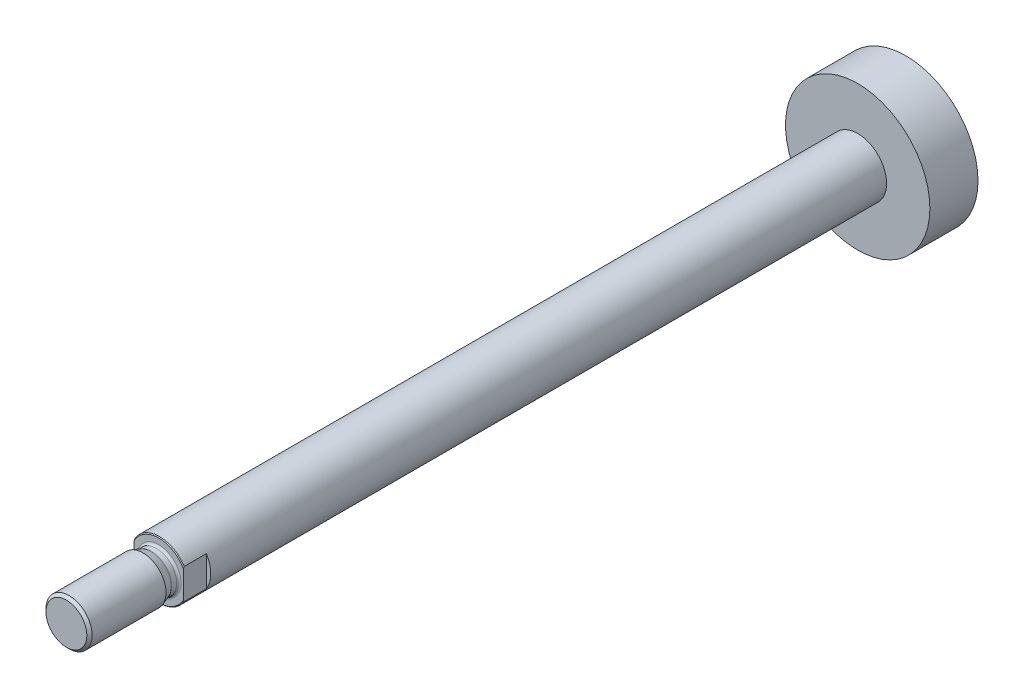
SolidWorks part; units mm, degrees
ref_plane "Front Plane" through (0, 0, 0) normal (0, 0, 1) x (1, 0, 0)
ref_plane "Top Plane" through (0, 0, 0) normal (0, 1, 0) x (1, 0, 0)
ref_plane "Right Plane" through (0, 0, 0) normal (1, 0, 0) x (0, 0, -1)
sketch "Sketch1" plane through (0, 0, 0) normal (1, 0, 0) x (0, 0, -1)
  line L0 (-35.8, 0) -> (-35.8, 9.7172)
  line L1 (-35.8, 9.7172) -> (-35.5172, 10)
  line L2 (-35.5172, 10) -> (206.3333, 10)
  line L3 (206.3333, 10) -> (206.3333, 25)
  line L4 (206.3333, 25) -> (223, 25)
  line L5 (223, 25) -> (223, 0)
  line L6 (223, 0) -> (-35.8, 0)
  line L7 (223, 0) -> (-35.8, 0) construction
revolve "Revolve1" add sketch "Sketch1" angle 360 about L7 reverse direction yes
ref_plane "Plane1" through (0, 0, -206.3333) normal (0, 0, 1) x (1, 0, 0)
sketch "Sketch2" plane through (0, 0, 0) normal (0, 1, 0) x (1, 0, 0)
  line L0 (-17, -61.8) -> (17, -61.8)
  line L1 (17, -61.8) -> (17, -27.8)
  line L2 (17, -27.8) -> (8.5, -27.8)
  line L3 (8.5, -27.8) -> (8.5, -43.8)
  line L4 (8.5, -43.8) -> (-8.5, -43.8)
  line L5 (-8.5, -43.8) -> (-8.5, -27.8)
  line L6 (-8.5, -27.8) -> (-17, -27.8)
  line L7 (-17, -27.8) -> (-17, -61.8)
extrude "Cut-Extrude1" cut sketch "Sketch2" along normal blind 17 and the other way blind 17
sketch "Sketch3" plane through (0, 0, 0) normal (1, 0, 0) x (0, 0, -1)
  line L0 (-67.8, 0) -> (-67.8, 7.08)
  line L1 (-67.8, 7.08) -> (-66.88, 8)
  line L2 (-66.88, 8) -> (-41.2849, 8)
  line L3 (-41.2849, 8) -> (-38.5243, 6.9952)
  line L4 (-38.2678, 6.95) -> (-36.55, 6.95)
  line L5 (-35.8, 7.7) -> (-35.05, 7.7)
  line L6 (-35.05, 7.7) -> (-35.05, 0)
  line L7 (-35.05, 0) -> (-67.8, 0)
  line L8 (-35.05, 0) -> (-67.8, 0) construction
  arc A0 (-38.5243, 6.9952) -> (-38.2678, 6.95) centre (-38.2678, 7.7) ccw
  arc A1 (-36.55, 6.95) -> (-35.8, 7.7) centre (-36.55, 7.7) ccw
revolve "Revolve2" add sketch "Sketch3" angle 360 about L8 reverse direction yes
cosmetic thread "Cosmetic Thread1" parameters "D1"=29.0428, "D2"=14.16
ref_plane "Plane2" through (0, 0, -223) normal (0, 0, 1) x (1, 0, 0)
ref_plane "Plane3" through (0, 0, 49.8) normal (0, 0, 1) x (1, 0, 0)
ref_plane "Plane4" through (0, 0, 49.8) normal (0, 0, 1) x (1, 0, 0)
ref_plane "FDT_PIRODACC XY" through (0, 0, 49.8) normal (0, 0, 1) x (1, 0, 0)
ref_plane "FDT_PIRODACC XZ" through (0, 0, 0) normal (0, -1, 0) x (-1, 0, 0)
ref_plane "FDT_PIRODACC YZ" through (0, 0, 0) normal (1, 0, 0) x (0, 0, -1)
ref_axis "FDT_PIRODACC X" through (-80.9, 0, 49.8) along (1, 0, 0)
ref_axis "FDT_PIRODACC Y" through (0, -50, 49.8) along (0, 1, 0)
ref_axis "FDT_PIRODACC Z" through (0, 0, 80.9) along (0, 0, -1)
sketch3d "FDT_PIRODACC"
  point P0 (0, 0, 49.8)
ref_plane "NUT XY" through (0, 0, 49.8) normal (0, 0, -1) x (-1, 0, 0)
ref_plane "NUT XZ" through (0, 0, 0) normal (0, 1, 0) x (1, 0, 0)
ref_plane "NUT YZ" through (0, 0, 0) normal (1, 0, 0) x (0, 0, -1)
ref_axis "NUT X" through (-80.9, 0, 49.8) along (1, 0, 0)
ref_axis "NUT Y" through (0, 50, 49.8) along (0, -1, 0)
ref_axis "NUT Z" through (0, 0, -80.9) along (0, 0, 1)
sketch3d "NUT"
  point P0 (0, 0, 49.8)
ref_plane "P XY" through (0, 0, -223) normal (0, 0, -1) x (-1, 0, 0)
ref_plane "P XZ" through (0, 0, 0) normal (-1, 0, 0) x (0, 0, 1)
ref_plane "P YZ" through (0, 0, 0) normal (0, 1, 0) x (1, 0, 0)
ref_axis "P X" through (0, -50, -223) along (0, 1, 0)
ref_axis "P Y" through (-80.9, 0, -223) along (1, 0, 0)
ref_axis "P Z" through (0, 0, -50) along (0, 0, 1)
sketch3d "P"
  point P0 (0, 0, -223)
